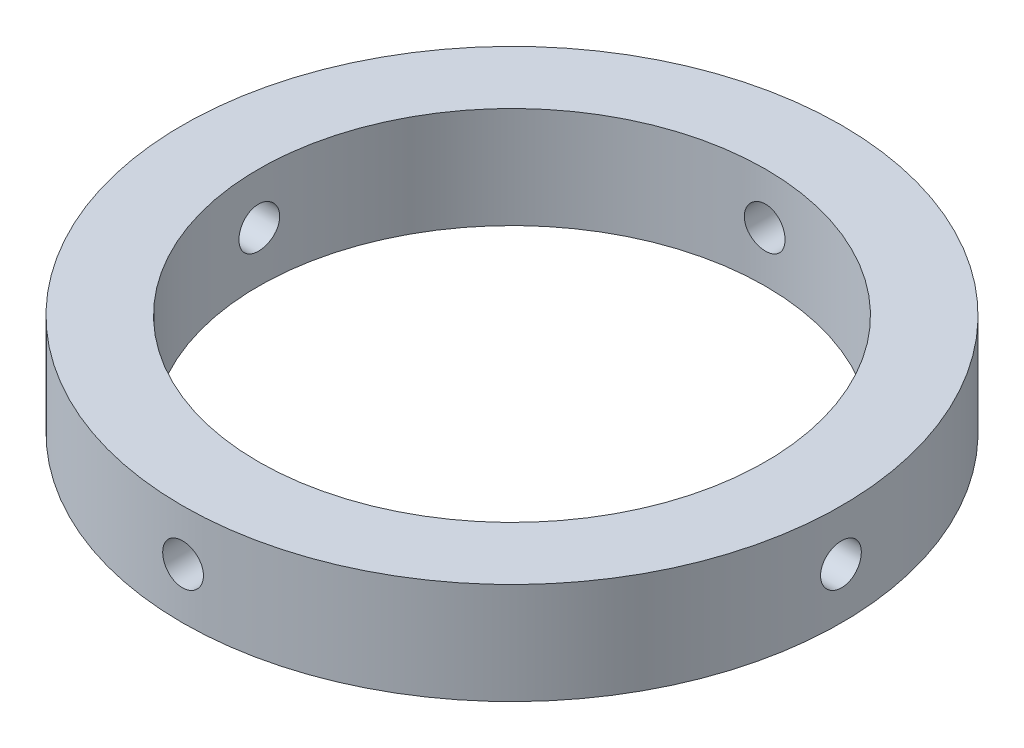
SolidWorks part; units mm, degrees
material "6061-T6 (SS)"
ref_plane "Front Plane" through (0, 0, 0) normal (0, 0, 1) x (1, 0, 0)
ref_plane "Top Plane" through (0, 0, 0) normal (0, 1, 0) x (1, 0, 0)
ref_plane "Right Plane" through (0, 0, 0) normal (1, 0, 0) x (0, 0, -1)
sketch "Sketch1" plane through (0, 0, 0) normal (0, 1, 0) x (1, 0, 0)
  circle A0 centre (0, 0) radius 31.75
  circle A1 centre (0, 0) radius 41.275
  dimension "D1" = 63.5
  dimension "D2" = 82.55
extrude "Boss-Extrude1" add sketch "Sketch1" along normal blind 12.7
ref_axis "Axis1" through (0, -0.3175, 0) along (0, 1, 0)
ref_plane "Plane1" through (0, 6.35, 0) normal (0, 1, 0) x (1, 0, 0)
ref_axis "Axis2" through (0, 6.35, -88.99) along (0, 0, 1)
hole_wizard "#7 (0.201) Diameter Hole1" positions "3DSketch2" profile "Sketch3" hole size "#7" standard "ANSI Inch"
sketch3d "3DSketch2"
  line L0 (0, 6.35, -88.99) -> (0, 6.35, 88.99) construction
  point P0 (0, 6.35, 41.275)
sketch "Sketch3" plane through (0, 6.35, 41.275) normal (1, 0, 0) x (0, -1, 0)
  line L0 (0, 0) -> (0, 13.2178)
  line L1 (0, 13.2178) -> (2.5527, 11.684)
  line L2 (2.5527, 11.684) -> (2.5527, 0)
  line L5 (2.5527, 0) -> (0, 0)
  line L10 (0, 13.2178) -> (-2.5527, 11.684) construction
  line L11 (0, -6.35) -> (0, 107.95) construction
  dimension "Hole Dia." = 5.1054
  dimension "Hole Depth" = 11.684
  dimension "Drill Angle" = 118
cosmetic thread "Cosmetic Thread2" parameters "D2"=6.35
pattern_circular "CirPattern1" count 4 over 360 about axis through (0, -0.3175, 0) along (0, 1, 0) of "#7 (0.201) Diameter Hole1"
